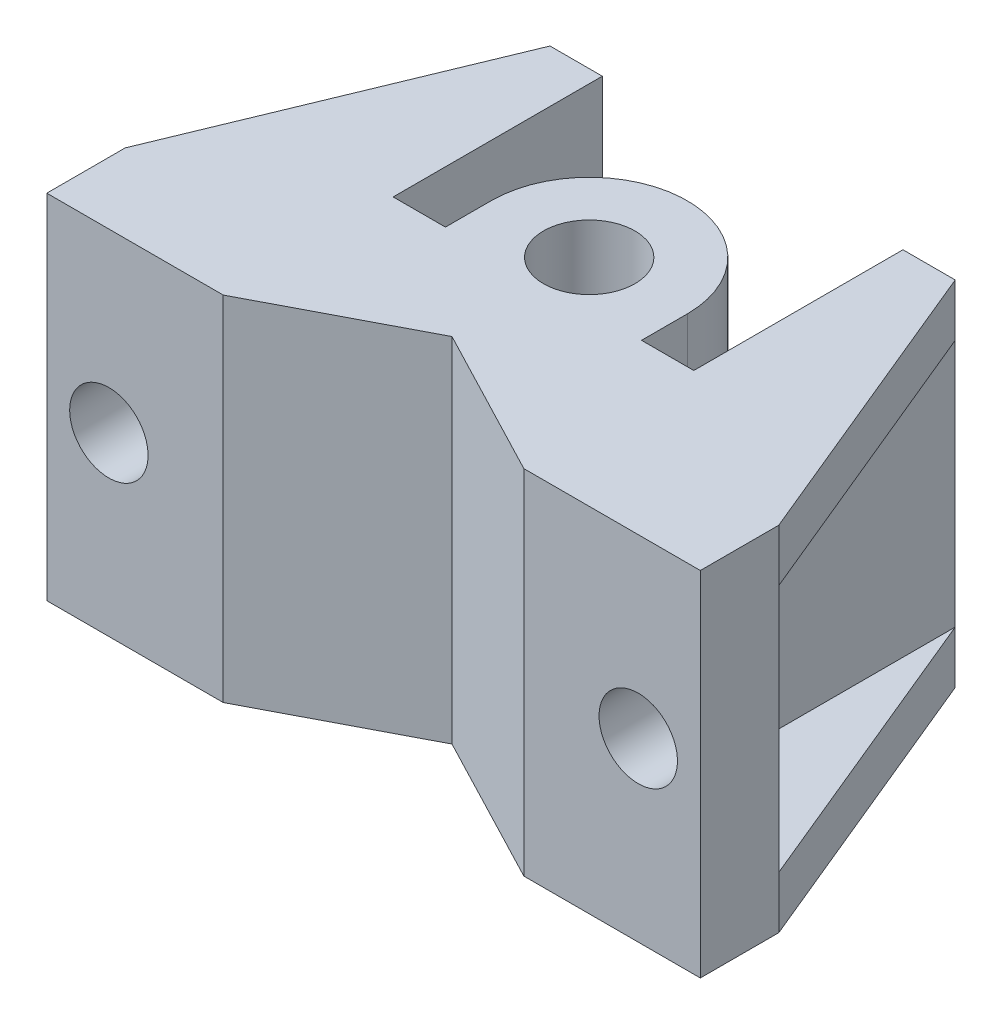
SolidWorks part; units mm, degrees
ref_plane "前视基准面" through (0, 0, 0) normal (0, 0, 1) x (1, 0, 0)
ref_plane "上视基准面" through (0, 0, 0) normal (0, 1, 0) x (1, 0, 0)
ref_plane "右视基准面" through (0, 0, 0) normal (1, 0, 0) x (0, 0, -1)
other "Configuration Table"
sketch "草图1" plane through (0, 0, 0) normal (0, 1, 0) x (1, 0, 0)
  line L0 (15, 0) -> (15, -7)
  line L1 (15, -7) -> (23, -7)
  line L2 (23, -7) -> (23, 25)
  line L3 (23, 25) -> (31, 25)
  line L4 (50, -21) -> (50, -33)
  line L5 (50, -33) -> (23, -33)
  line L6 (23, -33) -> (0, -21)
  line L7 (0, 0) -> (0, -137.7914) construction
  line L8 (-23, -33) -> (0, -21)
  line L9 (-50, -33) -> (-23, -33)
  line L10 (-50, -21) -> (-50, -33)
  line L11 (-31, 25) -> (-50, -21)
  line L12 (-23, -7) -> (-23, 25)
  line L13 (-15, -7) -> (-23, -7)
  line L14 (-15, 0) -> (-15, -7)
  line L15 (31, 25) -> (50, -21)
  line L16 (-23, 25) -> (-31, 25)
  circle A0 centre (0, 0) radius 7
  arc A1 (15, 0) -> (-15, 0) centre (0, 0) ccw
  point P21 (-57.1838, 33.0325)
  point P23 (0, -26.7972)
  dimension "D1" = 14
  dimension "D2" = 30
  dimension "D3" = 46
  dimension "D4" = 58
  dimension "D5" = 33
  dimension "D6" = 26
  dimension "D7" = 12
  dimension "D8" = 100
  dimension "D9" = 46
  dimension "D10" = 62
  dimension "D11" = 12
extrude "凸台-拉伸1" add sketch "草图1" along normal mid plane 54
sketch "草图2" plane through (0, 0, -25) normal (0, 0, -1) x (-1, 0, 0)
  line L0 (50, 27) -> (50, -27) construction
  line L1 (50, 19) -> (31, 19)
  line L2 (50, 19) -> (50, -19)
  line L3 (50, -19) -> (31, -19)
  line L4 (31, 19) -> (31, -19)
  line L5 (31, 27) -> (50, 27) construction
  line L6 (31, -27) -> (50, -27) construction
  line L7 (31, -27) -> (50, -27) construction
  line L8 (31, 27) -> (50, 27) construction
  line L9 (0, 0) -> (25.5884, 0) construction
  line L10 (31, 27) -> (31, -27) construction
  line L11 (50, 19) -> (31, -19) construction
  line L12 (0, 0) -> (0, 30.333) construction
  line L13 (-50, 19) -> (-31, -19) construction
  line L14 (-31, 19) -> (-31, -19)
  line L15 (-50, -19) -> (-31, -19)
  line L16 (-50, 19) -> (-50, -19)
  line L17 (-50, 19) -> (-31, 19)
  circle A1 centre (40.5, 0) radius 6
  circle A2 centre (-40.5, 0) radius 6
  dimension "D1" = 38
  dimension "D2" = 12
extrude "切除-拉伸1" cut sketch "草图2" against normal up to vertex (46 mm away) up to point (50, 27, 21)
extrude "切除-拉伸2" cut sketch "草图2<2>" against normal through all contours A1 | A2 region at (-40.5, 0, -25) region at (40.5, 0, -25)
sketch "草图2<2>" plane through (0, 0, -25) normal (0, 0, -1) x (-1, 0, 0) same geometry as "草图2"
